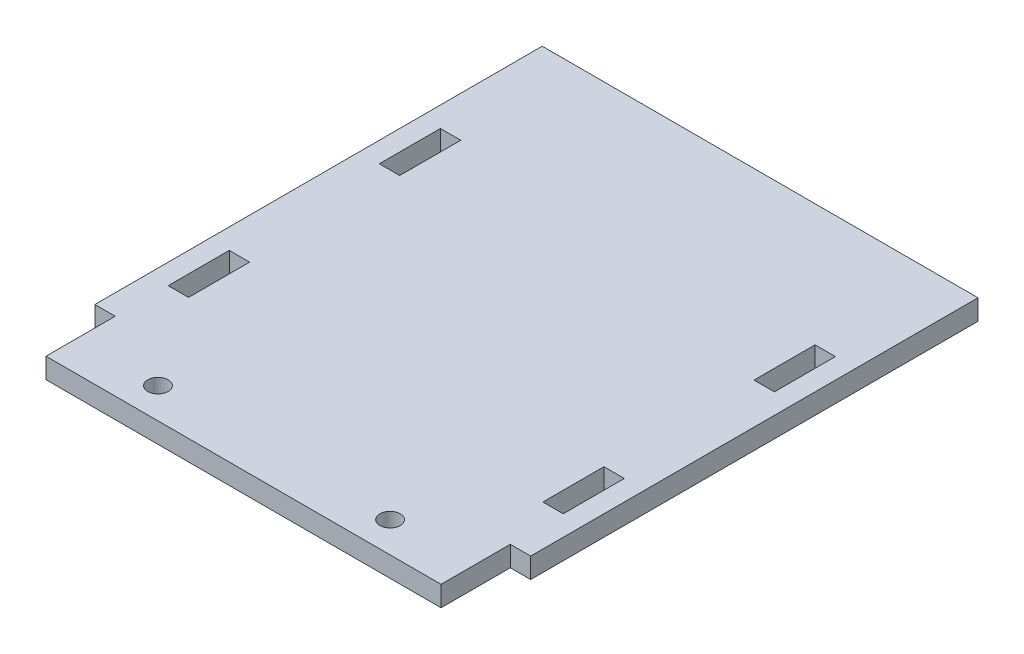
SolidWorks part; units mm, degrees
ref_plane "前视基准面" through (0, 0, 0) normal (0, 0, 1) x (1, 0, 0)
ref_plane "上视基准面" through (0, 0, 0) normal (0, 1, 0) x (1, 0, 0)
ref_plane "右视基准面" through (0, 0, 0) normal (1, 0, 0) x (0, 0, -1)
sketch "草图1" plane through (0, 0, 0) normal (0, 1, 0) x (1, 0, 0)
  line L1 (-48.5, -63.42) -> (48.5, -63.42)
  line L3 (-53.5, 63.42) -> (53.5, 63.42)
  line L5 (-53.5, -63.42) -> (53.5, 63.42) construction
  line L6 (-53.5, 63.42) -> (53.5, -63.42) construction
  line L23 (48.5, 33.42) -> (43.5, 33.42)
  line L24 (48.5, 33.42) -> (48.5, 18.42)
  line L25 (48.5, 18.42) -> (43.5, 18.42)
  line L26 (43.5, 33.42) -> (43.5, 18.42)
  line L27 (48.5, -18.42) -> (43.5, -18.42)
  line L28 (48.5, -18.42) -> (48.5, -33.42)
  line L29 (48.5, -33.42) -> (43.5, -33.42)
  line L30 (43.5, -18.42) -> (43.5, -33.42)
  line L31 (-43.5, 33.42) -> (-48.5, 33.42)
  line L32 (-43.5, 33.42) -> (-43.5, 18.42)
  line L33 (-43.5, 18.42) -> (-48.5, 18.42)
  line L34 (-48.5, 33.42) -> (-48.5, 18.42)
  line L35 (-43.5, -18.42) -> (-48.5, -18.42)
  line L36 (-43.5, -18.42) -> (-43.5, -33.42)
  line L37 (-43.5, -33.42) -> (-48.5, -33.42)
  line L38 (-48.5, -18.42) -> (-48.5, -33.42)
  line L42 (53.5, 63.42) -> (53.5, -46.42)
  line L43 (-53.5, 63.42) -> (-53.5, -46.42)
  line L44 (53.5, -46.42) -> (48.5, -46.42)
  line L45 (48.5, -46.42) -> (48.5, -63.42)
  line L46 (-53.5, -46.42) -> (-48.5, -46.42)
  line L47 (-48.5, -46.42) -> (-48.5, -63.42)
  circle A0 centre (-28.5, -55.9326) radius 2.5
  circle A1 centre (28.5, -55.9326) radius 2.5
  point P0 (0, 0)
  point P6 (-48.5, 25.92)
  point P13 (0, 0)
  dimension "D13" = 5
  dimension "D14" = 5
  dimension "D26" = 28.5
  dimension "D1" = 107
  dimension "D3" = 5
  dimension "D4" = 15
  dimension "D5" = 5
  dimension "D6" = 15
  dimension "D7" = 5
  dimension "D8" = 15
  dimension "D9" = 5
  dimension "D10" = 15
  dimension "D11" = 30
  dimension "D12" = 5
  dimension "D15" = 7.4874
  dimension "D16" = 5
  dimension "D17" = 7.4874
  dimension "D18" = 30
  dimension "D19" = 30
  dimension "D20" = 5
  dimension "D21" = 30
  dimension "D22" = 5
  dimension "D23" = 5
  dimension "D24" = 17
  dimension "D25" = 5
  dimension "D27" = 28.5
  dimension "D28" = 126.84
extrude "凸台-拉伸1" add sketch "草图1" along normal blind 5
